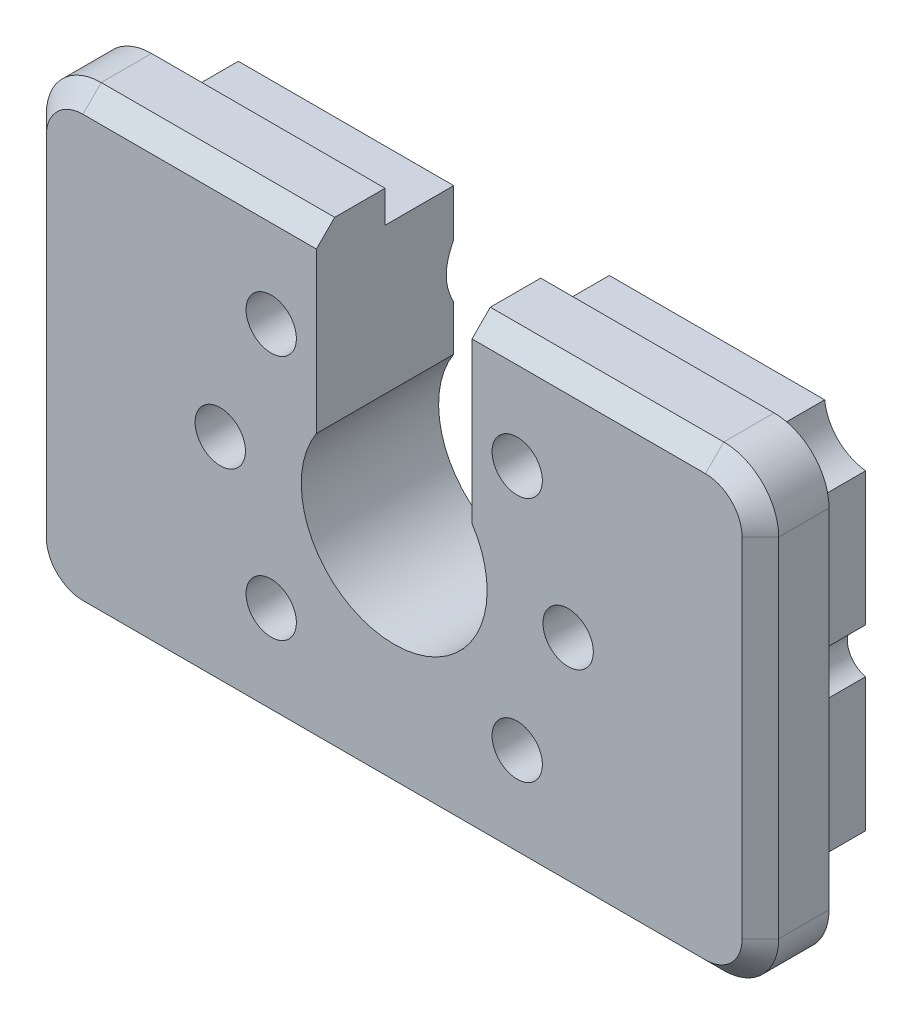
SolidWorks part; units mm, degrees
material "PET"
ref_plane "Front Plane" through (0, 0, 0) normal (0, 0, 1) x (1, 0, 0)
ref_plane "Top Plane" through (0, 0, 0) normal (0, 1, 0) x (1, 0, 0)
ref_plane "Right Plane" through (0, 0, 0) normal (1, 0, 0) x (0, 0, -1)
sketch "Sketch1" plane through (0, 0, 0) normal (0, 0, 1) x (1, 0, 0)
  line L1 (40, -25) -> (-40, -25)
  line L2 (40, -25) -> (40, 25)
  line L3 (40, 25) -> (-40, 25)
  line L4 (-40, -25) -> (-40, 25)
  line L5 (40, -25) -> (-40, 25) construction
  line L6 (40, 25) -> (-40, -25) construction
  point P0 (0, 0)
  dimension "D1" = 50
  dimension "D2" = 80
extrude "Boss-Extrude1" add sketch "Sketch1" against normal blind 7.5
sketch "Sketch2" plane through (0, 0, -7.5) normal (0, 0, -1) x (-1, 0, 0)
  line L8 (36.5, -21.5) -> (36.5, 21.5)
  line L9 (36.5, 21.5) -> (-36.5, 21.5)
  line L10 (-36.5, 21.5) -> (-36.5, -21.5)
  line L11 (-36.5, -21.5) -> (36.5, -21.5)
  line L12 (36.5, -21.5) -> (36.5, 21.5)
  line L13 (36.5, 21.5) -> (-36.5, 21.5)
  line L14 (-36.5, 21.5) -> (-36.5, -21.5)
  line L15 (-36.5, -21.5) -> (36.5, -21.5)
  dimension "D1" = 3.5
extrude "Boss-Extrude2" add sketch "Sketch2" along normal blind 7.5
sketch "Sketch3" plane through (0, 0, 0) normal (0, 0, 1) x (1, 0, 0)
  line L0 (0, 0) -> (0, 51.1675) construction
  line L1 (40, 25) -> (-40, 25) construction
  line L2 (8.5, 5.5473) -> (-8.5, 5.5473) construction
  line L3 (8.5, 5.5473) -> (8.5, 25)
  line L4 (8.5, 25) -> (-8.5, 25)
  line L5 (-8.5, 5.5473) -> (-8.5, 25)
  line L6 (8.5, 5.5473) -> (-8.5, 25) construction
  line L7 (8.5, 25) -> (-8.5, 5.5473) construction
  line L8 (0, 0) -> (-19, 0) construction
  arc A0 (-8.5, 5.5473) -> (8.5, 5.5473) centre (0, 0) ccw
  circle A1 centre (-19, 0) radius 2.75
  circle A2 centre (-13.435, 13.435) radius 2.75
  circle A3 centre (0, 19) radius 2.75 construction
  circle A4 centre (13.435, 13.435) radius 2.75
  circle A5 centre (19, 0) radius 2.75
  circle A6 centre (13.435, -13.435) radius 2.75
  circle A7 centre (0, -19) radius 2.75 construction
  circle A8 centre (-13.435, -13.435) radius 2.75
  point P3 (0, 15.2736)
  point P28 (0, 0)
  dimension "D4" = 5.5
  dimension "D2" = 17
  dimension "D3" = 19
  dimension "D5" = 8
extrude "Cut-Extrude1" cut sketch "Sketch3" against normal through all
fillet "Fillet1" radius 6 4 edges at (40, -25, -3.75) (-40, -25, -3.75) (-40, 25, -3.75) (40, 25, -3.75)
sketch "Sketch4" plane through (0, 0, -15) normal (0, 0, -1) x (-1, 0, 0)
  line L0 (-37, 22) -> (-37, -22) construction
  line L1 (-40, -19) -> (-40, 19) construction
  line L2 (-34, 25) -> (-8.5, 25) construction
  line L4 (34, -25) -> (-34, -25) construction
  line L5 (-37, -22) -> (0, -22) construction
  line L6 (0, 0) -> (0, -22) construction
  circle A0 centre (-37, 22) radius 5
  circle A1 centre (-37, -22) radius 5
  circle A2 centre (-37, 0) radius 2.5
  circle A3 centre (0, -22) radius 2.5
  circle A4 centre (37, -22) radius 5
  circle A5 centre (37, 0) radius 2.5
  circle A6 centre (37, 22) radius 5
  dimension "D4" = 5
  dimension "D5" = 10
  dimension "D1" = 3
  dimension "D2" = 3
  dimension "D3" = 3
extrude "Cut-Extrude2" cut sketch "Sketch4" against normal up to surface (7.5 mm away) up to face at (0, 5.8125, -7.5)
chamfer "Chamfer1" distance 2 angle 45 9 edges at (-21.25, 25, 0) (-38.2426, 23.2426, 0) (-40, 0, 0) (-38.2426, -23.2426, 0) (0, -25, 0) (38.2426, -23.2426, 0) (40, 0, 0) (38.2426, 23.2426, 0) (21.25, 25, 0)
chamfer "Chamfer2" distance 3 angle 45 6 edges at (16.185, -13.435, -15) (-16.25, 0, -15) (-10.685, -13.435, -15) (21.75, 0, -15) (16.185, 13.435, -15) (-10.685, 13.435, -15)
equation "\"hole_radius\"= 10.15mm"
equation "\"D1@Sketch3\"=\"hole_radius\"*2"
equation "\"M5_tap\"=4.2mm"
equation "\"M5_clearence\"=5.5mm"
equation "\"M6_tap\"=5mm"
equation "\"M6_clearence\"=6.6mm"
equation "\"work_area_width\"=1100mm"
equation "\"work_area_depth\"=900mm"
equation "\"steel_base_width\"=80mm"
equation "\"steel_base_height\"=50mm"
equation "\"steel_base_wall_thickness\"=3mm"
equation "\"steel_base_radius\"=6mm"
equation "\"steel_sides_width\"=80mm"
equation "\"steel_sides_height\"=50mm"
equation "\"steel_sides_wall_thickness\"=5mm"
equation "\"steel_sides_radius\"=6mm"
equation "\"steel_gantry_width\"=80mm"
equation "\"steel_gantry_height\"=50mm"
equation "\"steel_gantry_wall_thickness\"=6mm"
equation "\"steel_gantry_radius\"=6mm"
equation "\"steel_rollers_width\"=80mm"
equation "\"steel_rollers_height\"=50mm"
equation "\"steel_rollers_wall_thickness\"=6mm"
equation "\"steel_rollers_radius\"=6mm"
equation "\"steel_zbox_width\"=80mm"
equation "\"steel_zbox_height\"=50mm"
equation "\"steel_zbox_wall_thickness\"=3mm"
equation "\"steel_zbox_radius\"=6mm"
equation "\"D2@Sketch1\"=\"steel_zbox_width\""
equation "\"D1@Sketch1\"=\"steel_zbox_height\""
equation "\"D1@Sketch2\"=\"steel_zbox_wall_thickness\"+ 0.5mm"
equation "\"D1@Fillet1\"=\"steel_zbox_radius\""
